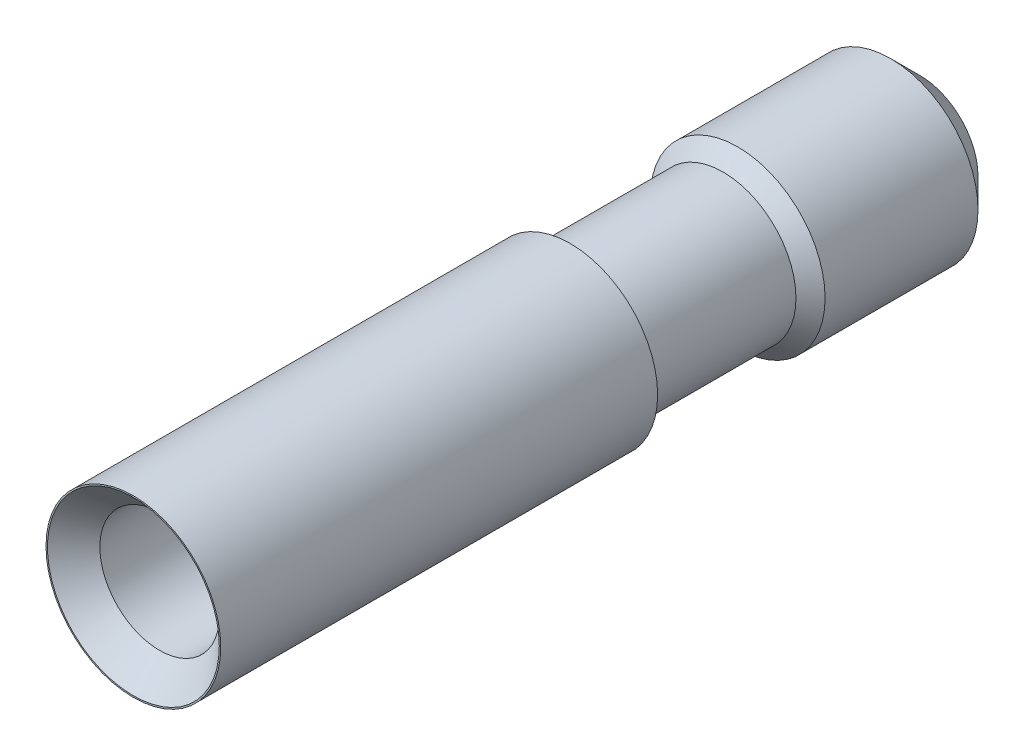
SolidWorks part; units mm, degrees
ref_plane "Plan de face" through (0, 0, 0) normal (0, 0, 1) x (1, 0, 0)
ref_plane "Plan de dessus" through (0, 0, 0) normal (0, 1, 0) x (1, 0, 0)
ref_plane "Plan de droite" through (0, 0, 0) normal (1, 0, 0) x (0, 0, -1)
sketch "Esquisse1" plane through (0, 0, 0) normal (0, 0, 1) x (1, 0, 0)
  circle A0 centre (0, 0) radius 3
  dimension "D1" = 6
extrude "Boss.-Extru.1" add sketch "Esquisse1" along normal blind 27 contours A0
cosmetic thread "Représentation de filetage1" parameters "D1"=5, "D2"=4.891
sketch "Esquisse7" plane through (0, 0, 27) normal (0, 0, 1) x (1, 0, 0)
  circle A1 centre (0, 0) radius 2.05
  dimension "D1" = 4.1
hole_wizard "Diamètre du perçage Ø2.5 (2.5)2" positions "Esquisse5" profile "Esquisse4" hole size "Ø2.5" standard "ISO"
sketch "Esquisse5" plane through (0, 0, 0) normal (0, 0, -1) x (-1, 0, 0)
  point P0 (0, 0)
sketch "Esquisse4" plane through (0, 0, 0) normal (1, 0, 0) x (0, 1, 0)
  line L0 (0, 0) -> (0, 3.7511)
  line L1 (0, 3.7511) -> (1.25, 3)
  line L2 (1.25, 3) -> (1.25, 0)
  line L5 (1.25, 0) -> (0, 0)
  line L10 (0, 3.7511) -> (-1.25, 3) construction
  line L11 (0, -6.35) -> (0, 107.95) construction
  dimension "Diamètre du perçage" = 2.5
  dimension "Profondeur du perçage" = 3
  dimension "Angle de pointe" = 118
sketch "Esquisse6" plane through (0, 0, 27) normal (0, 0, 1) x (1, 0, 0)
  line L1 (-6.0949, -5.2635) -> (5.6553, -5.2635)
  line L2 (-6.0949, -5.2635) -> (-6.0949, 6.1211)
  line L3 (-6.0949, 6.1211) -> (5.6553, 6.1211)
  line L4 (5.6553, -5.2635) -> (5.6553, 6.1211)
  circle A0 centre (0, 0) radius 2.5
  dimension "D1" = 5
extrude "Enlèv. mat.-Extru.1" cut sketch "Esquisse6" against normal blind 6 from offset 15 offset against normal yes
chamfer "Chanfrein1" distance 1 angle 45 1 edges at (3, 0, 0)
chamfer "Chanfrein2" distance 0.75 angle 45 1 edges at (2.5, 0, 6)
extrude "Enlèv. mat.-Extru.2" cut sketch "Esquisse7" against normal blind 24.5
chamfer "Chanfrein4" distance 0.9 angle 45 1 edges at (2.05, 0, 27)
